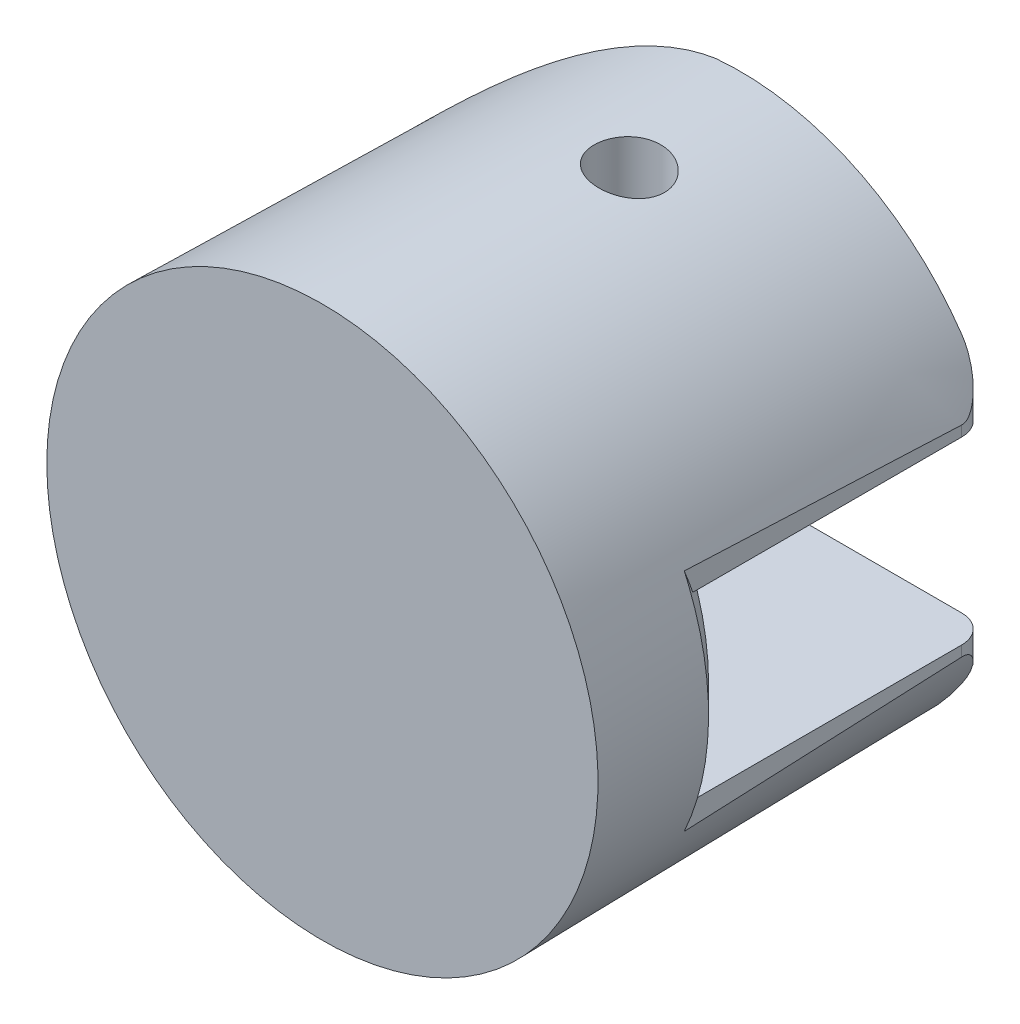
SolidWorks part; units mm, degrees
ref_plane "Plan de face" through (0, 0, 0) normal (0, 0, 1) x (1, 0, 0)
ref_plane "Plan de dessus" through (0, 0, 0) normal (0, 1, 0) x (1, 0, 0)
ref_plane "Plan de droite" through (0, 0, 0) normal (1, 0, 0) x (0, 0, -1)
sketch "Sketch1" plane through (0, 0, 0) normal (0, 0, 1) x (1, 0, 0)
  circle A0 centre (0, 0) radius 10
  dimension "D1" = 20
extrude "Boss-Extrude1" add sketch "Sketch1" along normal blind 18
sketch "Sketch2" plane through (0, 0, 0) normal (0, 1, 0) x (1, 0, 0)
  line L0 (-8, -10) -> (-16.4398, -10)
  line L1 (-16.4398, -10) -> (-16.4398, 10.405)
  line L2 (-16.4398, 10.405) -> (23.4224, 10.405)
  line L3 (23.4224, 10.405) -> (23.4224, -10)
  line L4 (23.4224, -10) -> (9, -10)
  line L5 (-10, 0) -> (-10, -18) construction
  line L6 (-10, -18) -> (10, -18) construction
  line L7 (9, -10) -> (9, 0)
  line L8 (10, 0) -> (-10, 0) construction
  line L9 (9, 0) -> (-0.88, 0)
  line L10 (-8, -10) -> (-7.3114, -5.8406)
  arc A0 (-7.3114, -5.8406) -> (-0.88, 0) centre (-0.4054, -6.9839) cw
  dimension "D5" = 7
  dimension "D1" = 2
  dimension "D2" = 8
  dimension "D3" = 17
  dimension "D4" = 9.88
  dimension "D6" = 80.6
  dimension "D7" = 4.216
extrude "Cut-Extrude1" cut sketch "Sketch2" against normal blind 18 and the other way blind 18 contours L10 A0 L9 L7 L4 L3 L2 L1 L0 region at (4.0327, 0, -1.4851)
sketch "Sketch3" plane through (0, 0, 0) normal (0, 1, 0) x (1, 0, 0)
  line L0 (-10, -18) -> (10, -18) construction
  line L1 (10, -18) -> (10, -10) construction
  circle A0 centre (1, -5) radius 1.25
  dimension "D3" = 2.5
  dimension "D1" = 13
  dimension "D2" = 9
extrude "Cut-Extrude2" cut sketch "Sketch3" against normal mid plane 24
sketch "Sketch4" plane through (0, 0, 18) normal (0, 0, 1) x (1, 0, 0)
  circle A0 centre (0, 0) radius 10
extrude "Cut-Extrude-Thin6" cut sketch "Sketch4" against normal blind 23.25 draft 1 thin contours A0 draft outward yes thin type one direction wall 10
sketch "Sketch5" plane through (0, 0, 0) normal (0, 1, 0) x (1, 0, 0)
  line L0 (9, -10) -> (9, 0) construction
  line L1 (-8, -10) -> (9, -10)
  line L2 (-8, -10) -> (-8, 5.0795)
  line L3 (-8, 5.0795) -> (9, 5.0795)
  line L4 (9, -10) -> (9, 5.0795)
extrude "Cut-Extrude3" cut sketch "Sketch5" against normal blind 3.25 and the other way blind 3.25
fillet "Fillet1" radius 1 2 edges at (9, 3.4149, 0) (9, -3.4149, 0)
sketch "Sketch6" plane through (0, 0, 0) normal (0, 1, 0) x (1, 0, 0)
  line L0 (-10, -18) -> (10, -18) construction
  line L1 (12.6946, -15.08) -> (-11.7994, -15.08)
  line L2 (12.6946, -15.08) -> (12.6946, -19.0549)
  line L3 (12.6946, -19.0549) -> (-11.7994, -19.0549)
  line L4 (-11.7994, -15.08) -> (-11.7994, -19.0549)
  dimension "D1" = 2.92
extrude "Cut-Extrude4" cut sketch "Sketch6" against normal mid plane 27.25
chamfer "Chamfer1" distance 1 angle 45 1 edges at (9.8604, 0, 10) first distance on face at (0.375, 0, 10)
